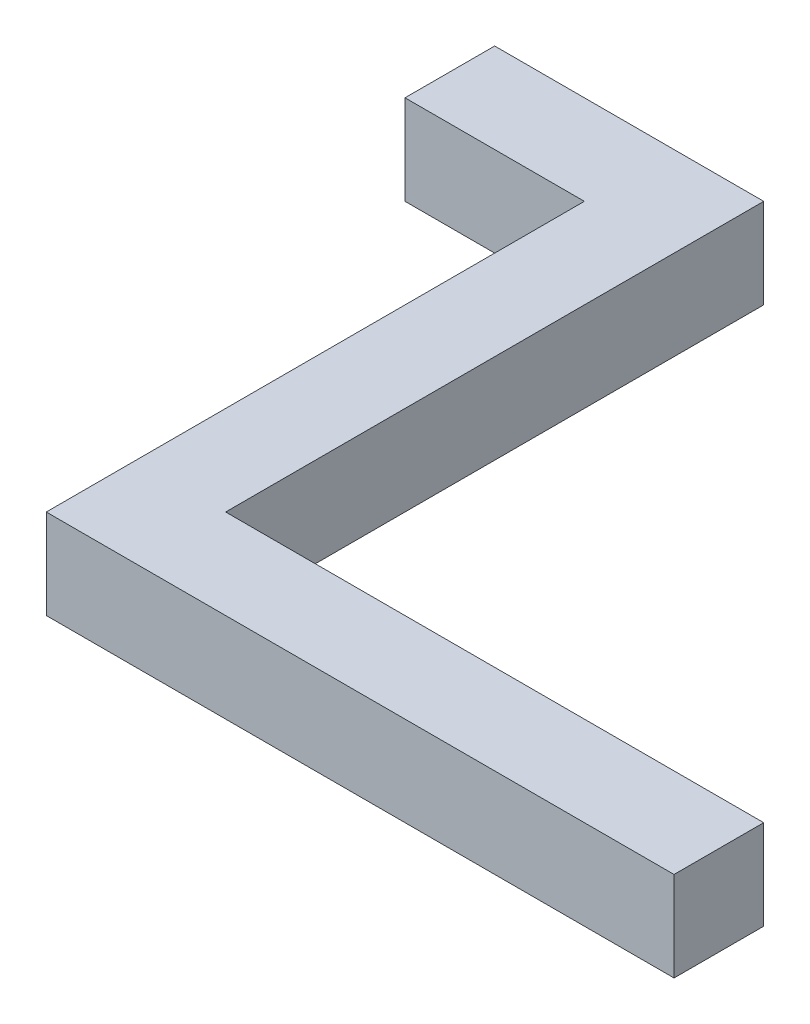
SolidWorks part; units mm, degrees
ref_plane "Front Plane" through (0, 0, 0) normal (0, 0, 1) x (1, 0, 0)
ref_plane "Top Plane" through (0, 0, 0) normal (0, 1, 0) x (1, 0, 0)
ref_plane "Right Plane" through (0, 0, 0) normal (1, 0, 0) x (0, 0, -1)
sketch "Sketch1" plane through (0, 0, 0) normal (0, 1, 0) x (1, 0, 0)
  line L0 (0, 0) -> (60, 0)
  line L1 (0, 0) -> (0, -20)
  line L2 (60, 0) -> (60, -68.077)
  line L3 (0, -20) -> (40, -20)
  line L5 (40, -20) -> (40, -140)
  line L6 (60, -68.077) -> (60, -120)
  line L7 (40, -140) -> (126.9375, -140)
  line L8 (126.9375, -140) -> (180, -140)
  line L10 (180, -140) -> (180, -120)
  line L11 (60, -120) -> (180, -120)
  point P0 (350.7574, -120.3477)
  dimension "D1" = 60
  dimension "D2" = 20
  dimension "D4" = 20
  dimension "D5" = 120
  dimension "D6" = 20
  dimension "D7" = 120
extrude "Boss-Extrude1" add sketch "Sketch1" along normal blind 20
